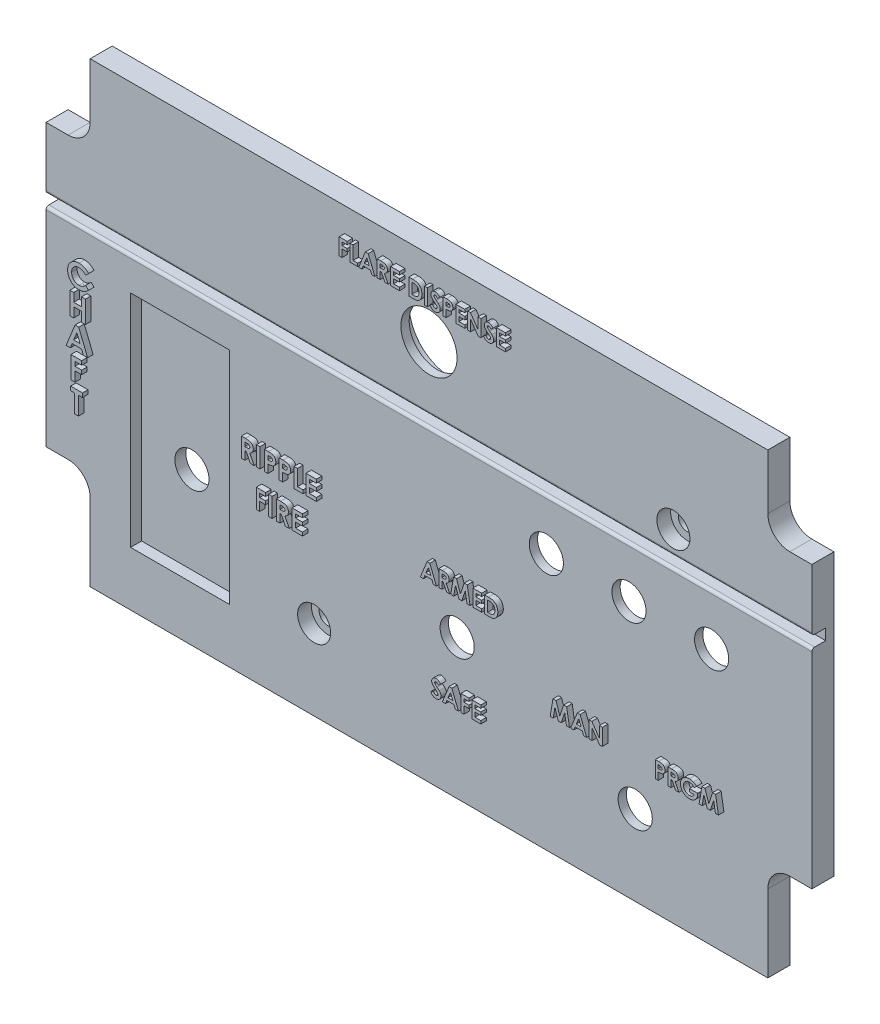
SolidWorks part; units mm, degrees
ref_plane "Front Plane" through (0, 0, 0) normal (0, 0, 1) x (1, 0, 0)
ref_plane "Top Plane" through (0, 0, 0) normal (0, 1, 0) x (1, 0, 0)
ref_plane "Right Plane" through (0, 0, 0) normal (1, 0, 0) x (0, 0, -1)
sketch "Sketch1" plane through (0, 0, 0) normal (0, 0, 1) x (1, 0, 0)
  line L1 (8, 6.6454) -> (131, 6.6454)
  line L2 (0, 24.6454) -> (0, 75.6454)
  line L3 (8, 89.6454) -> (131, 89.6454)
  line L4 (139, 24.6454) -> (139, 75.6454)
  line L13 (8, 89.6454) -> (8, 79.6454)
  line L14 (4, 75.6454) -> (0, 75.6454)
  line L15 (8, 6.6454) -> (8, 20.6454)
  line L16 (4, 24.6454) -> (0, 24.6454)
  line L17 (131, 89.6454) -> (131, 79.6454)
  line L18 (135, 75.6454) -> (139, 75.6454)
  line L19 (131, 6.6454) -> (131, 20.6454)
  line L20 (135, 24.6454) -> (139, 24.6454)
  line L23 (0, 0) -> (0, 87.0008) construction
  arc A8 (8, 20.6454) -> (4, 24.6454) centre (4, 20.6454) ccw
  arc A9 (8, 79.6454) -> (4, 75.6454) centre (4, 79.6454) cw
  arc A11 (131, 20.6454) -> (135, 24.6454) centre (135, 20.6454) cw
  arc A12 (131, 79.6454) -> (135, 75.6454) centre (135, 79.6454) ccw
  circle A14 centre (48.6544, 21.1904) radius 1.6 construction
  circle A15 centre (48.6544, 21.1904) radius 1.6
  circle A16 centre (90.8006, 53.2423) radius 3.1 construction
  circle A17 centre (105.8006, 53.2423) radius 3.1 construction
  circle A18 centre (120.8006, 53.2423) radius 3.1 construction
  circle A19 centre (90.8006, 53.2423) radius 3.1
  circle A35 centre (105.8006, 53.2423) radius 3.1
  circle A37 centre (120.8006, 53.2423) radius 3.1
  circle A47 centre (69.5, 75.8772) radius 5.1 construction
  circle A48 centre (106.9326, 21.1904) radius 3.1 construction
  circle A49 centre (74.6156, 32.0065) radius 3.1 construction
  circle A50 centre (24.475, 32.312) radius 3.1 construction
  circle A51 centre (69.5, 75.8772) radius 5.1
  circle A52 centre (106.9326, 21.1904) radius 3.1
  circle A53 centre (74.6156, 32.0065) radius 3.1
  circle A54 centre (24.475, 32.312) radius 3.1
  circle A55 centre (113.8581, 68.5981) radius 1.6 construction
  circle A56 centre (113.8581, 68.5981) radius 1.6
  point P21 (131, 24.6454)
  point P25 (8, 75.6454)
  point P40 (131, 75.6454)
  dimension "D3" = 18
  dimension "D4" = 14
  dimension "D5" = 8
  dimension "D7" = 83
  dimension "D11" = 8
  dimension "D16" = 139
  dimension "D22" = 8
  dimension "D9" = 8
extrude "Boss-Extrude1" add sketch "Sketch1" along normal blind 4
sketch "Sketch4" plane through (0, 0, 4) normal (0, 0, 1) x (1, 0, 0)
  line L0 (8, 54.5551) -> (8, 14.5758) construction
  line L1 (8, 89.6454) -> (8, 79.6454) construction
  line L2 (-3.2263, 38.4147) -> (14.9404, 38.4147) construction
  line L3 (-3.2263, 33.4147) -> (15.4271, 33.4147) construction
  line L4 (-2.9665, 53.4147) -> (15.2002, 53.4147) construction
  line L5 (-2.9665, 48.4147) -> (15.2002, 48.4147) construction
  line L6 (-2.9665, 43.4147) -> (15.2002, 43.4147) construction
  line L7 (5, 54.5551) -> (5, 14.5758) construction
  text T0 "<b>C</b>" font "Century Gothic" height 4
  text T1 "<b>T</b>" font "Century Gothic" height 4
  text T2 "<b>RIPPLE</b>\r\n<b>  FIRE</b>" font "Century Gothic" height 3.5
  text T5 "<b>F</b>" font "Century Gothic" height 4
  text T7 "<b>FLARE DISPENSE</b>" font "Century Gothic" height 3
  text T9 "<b>H</b>" font "Century Gothic" height 4
  text T10 "<b>A</b>" font "Century Gothic" height 4
  text T11 "<b>ARMED</b>" font "Century Gothic" height 3
  text T12 "<b>SAFE</b>" font "Century Gothic" height 3
  text T13 "<b>MAN</b>" font "Century Gothic" height 3
  text T15 "<b>PRGM</b>" font "Century Gothic" height 3
  dimension "D1" = 3
  dimension "D2" = 5
  dimension "D3" = 5
  dimension "D4" = 5
  dimension "D5" = 5
extrude "Textos" add sketch "Sketch4" along normal blind 1
sketch "Sketch8" plane through (0, 0, 4) normal (0, 0, 1) x (1, 0, 0)
  line L2 (33.3358, 56.5063) -> (15.3354, 56.5063)
  line L3 (33.3358, 56.5063) -> (33.3358, 16.5063)
  line L4 (33.3358, 16.5063) -> (15.3354, 16.5063)
  line L5 (15.3354, 56.5063) -> (15.3354, 16.5063)
  dimension "D1" = 40
  dimension "D2" = 18.0004
extrude "Cut-Extrude3" cut sketch "Sketch8" against normal blind 2
sketch "Sketch9" plane through (0, 0, 4) normal (0, 0, 1) x (1, 0, 0)
  line L0 (0, 75.6454) -> (0, 24.6454) construction
  line L1 (0, 64.4226) -> (139, 64.4226)
  line L2 (0, 64.4226) -> (0, 62.4226)
  line L3 (0, 62.4226) -> (139, 62.4226)
  line L4 (139, 64.4226) -> (139, 62.4226)
  line L5 (139, 24.6454) -> (139, 75.6454) construction
  dimension "D1" = 2
extrude "Cut-Extrude4" cut sketch "Sketch9" against normal blind 2.5
fillet "Fillet1" radius 0.5 2 edges at (69.5, 62.4226, 4) (69.5, 64.4226, 4)
sketch "Sketch10" plane through (0, 0, 4) normal (0, 0, 1) x (1, 0, 0)
  circle A0 centre (48.6544, 21.1904) radius 3
  circle A1 centre (113.8581, 68.5981) radius 3
  dimension "D1" = 6
extrude "Cut-Extrude5" cut sketch "Sketch10" against normal blind 2.5
sketch "Sketch11" plane through (0, 0, 0) normal (0, 0, -1) x (-1, 0, 0)
  circle A0 centre (-69.5, 75.8772) radius 7.6
  circle A1 centre (-90.8006, 53.2423) radius 6.7
  circle A2 centre (-105.8006, 53.2423) radius 6.7
  circle A3 centre (-120.8006, 53.2423) radius 6.7
  circle A5 centre (-74.6156, 32.0065) radius 6.7
  circle A6 centre (-106.9326, 21.1904) radius 6.7
  dimension "D1" = 15.2
  dimension "D2" = 13.4
extrude "Back holes" cut sketch "Sketch11" against normal blind 2.5
